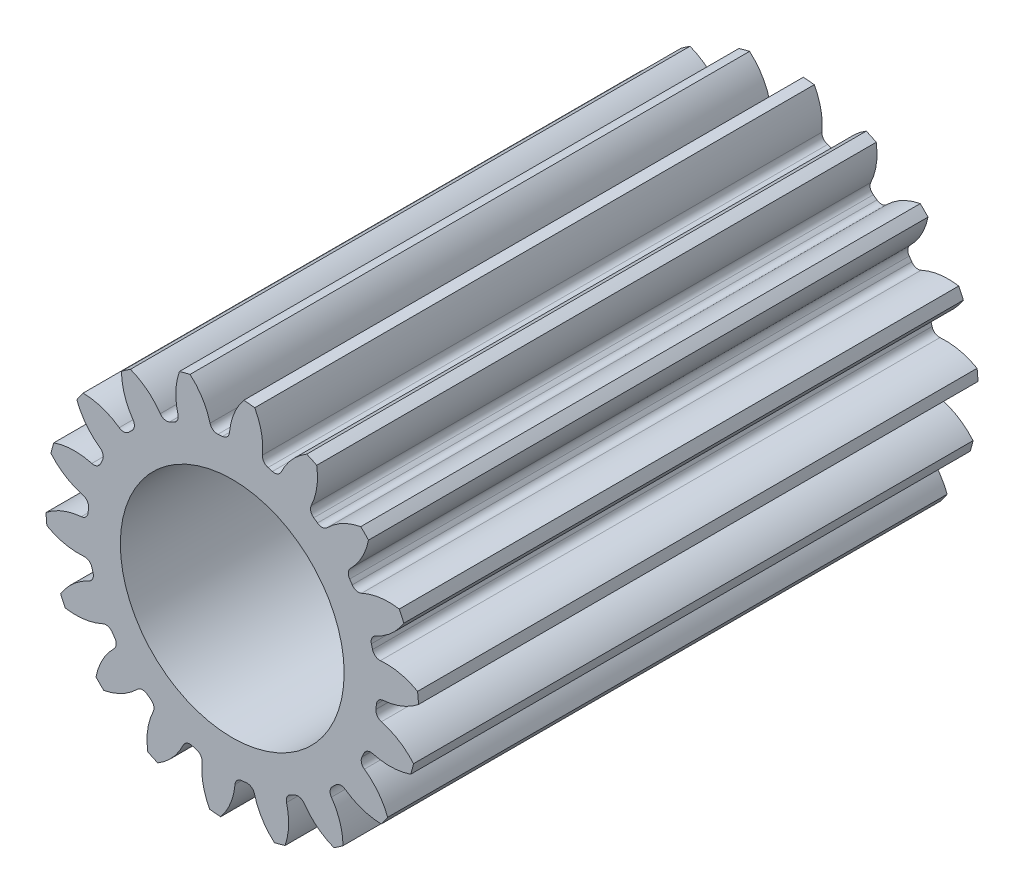
SolidWorks part; units mm, degrees
material "AISI 1045 Steel, cold drawn"
ref_plane "Front" through (0, 0, 0) normal (0, 0, 1) x (1, 0, 0)
ref_plane "Top" through (0, 0, 0) normal (0, 1, 0) x (1, 0, 0)
ref_plane "Right" through (0, 0, 0) normal (1, 0, 0) x (0, 0, -1)
sketch "Sketch3" plane through (0, 0, 0) normal (0, 0, 1) x (1, 0, 0)
  circle A0 centre (0, 0) radius 10
  dimension "od" = 20
extrude "gearBody" add sketch "Sketch3" along normal blind 30
sketch "Sketch2" plane through (0, 0, 0) normal (0, 0, 1) x (1, 0, 0)
  line L0 (0, 0) -> (7.8135, 3.2364) construction
  line L1 (10.2652, -3.2048) -> (0, 0) construction
  line L2 (0, 0) -> (36.3143, 0) construction
  line L3 (9, -0.0203) -> (8.8534, -1.6177) construction
  line L5 (8.9267, -0.819) -> (0, 0) construction
  line L7 (0, 0) -> (8.4572, 0) construction
  arc A0 (8.4555, -0.1697) -> (8.3452, -1.3717) centre (0, 0) ccw construction
  arc A1 (9.9857, 0.5354) -> (9.7215, -2.3435) centre (0, 0) ccw construction
  arc A2 (9, -0.0203) -> (8.8534, -1.6177) centre (0, 0) ccw construction
  arc A3 (7.7047, -0.8296) -> (7.727, -0.5863) centre (0, 0) ccw
  arc A4 (10.2652, -3.2048) -> (7.9976, -1.2579) centre (7.0941, -4.6042) ccw
  arc A5 (10.2652, -3.2048) -> (10.677, 1.2834) centre (0, 0) ccw
  arc A6 (10.677, 1.2834) -> (8.093, -0.2184) centre (7.8135, 3.2364) cw
  arc A7 (7.727, -0.5863) -> (8.093, -0.2184) centre (8.1252, -0.6165) cw
  arc A8 (7.9976, -1.2579) -> (7.7047, -0.8296) centre (8.1017, -0.8723) cw
  point P6 (10.677, 1.2834)
  point P22 (10.2652, -3.2048)
  dimension "baseDia" = 16.9145
  dimension "od" = 20
  dimension "pd" = 18
  dimension "rd" = 15.4984
  dimension "rFillet" = 0.3993
  dimension "pointX" = 10.677
  dimension "pointY" = 1.2834
  dimension "CTT" = 1.5974
  dimension "flankCenterAngle" = 22.5
extrude "toothCut" cut sketch "Sketch2" along normal through all
pattern_circular "CirPattern1" count 18 over 360 about axis through (0, 0, 30) along (0, 0, -1) of "toothCut"
ref_axis "toothSpace" through (0, 0, 0) along (0.9958, -0.0914, 0)
ref_axis "Axis2" through (9.6482, -2.629, 0) along (-0.9648, 0.2629, 0)
sketch "hub1Dia" plane through (0, 0, 0) normal (0, 0, -1) x (-1, 0, 0)
  circle A0 centre (0, 0) radius 0.5
  dimension "hub1Dia" = 1
sketch "hub2Dia" plane through (0, 0, 30) normal (0, 0, 1) x (1, 0, 0)
  circle A0 centre (0, 0) radius 0.5
  dimension "hub2dia" = 1
sketch "boreDia" plane through (0, 0, 0) normal (0, 0, 1) x (1, 0, 0)
  circle A0 centre (0, 0) radius 6
  dimension "boreDia" = 12
extrude "bore" cut sketch "boreDia" against normal mid plane 25400
sketch "kwy1sketch" plane through (0, 0, 0) normal (0, 0, 1) x (1, 0, 0)
  line L0 (-5.2713, 1.1117) -> (0, 0) construction
  line L1 (6.9525, -0.9552) -> (6.7462, -1.9337)
  line L2 (6.7462, -1.9337) -> (5.5231, -1.6758)
  line L3 (6.9525, -0.9552) -> (5.7294, -0.6973)
  line L4 (5.5231, -1.6758) -> (0, 0)
  line L5 (0, 0) -> (5.7294, -0.6973)
  line L6 (0, 0) -> (7.7168, -0.708) construction
  line L7 (6.8493, -1.4445) -> (0, 0) construction
  arc A7 (7.7047, -0.8296) -> (7.727, -0.5863) centre (0, 0) ccw construction
  point P9 (6.8493, -1.4445)
  point P13 (-0.8793, 0.1854)
  dimension "kwy1width" = 1
  dimension "kwy1depth" = 7
  dimension "kwy1angle" = 6.667
  dimension "kwy1Depth2" = 1.25
sketch "kwy2sketch" plane through (0, 0, 0) normal (0, 0, 1) x (1, 0, 0)
  line L0 (7.7168, -0.708) -> (0, 0) construction
  line L1 (0, 0) -> (-3.119, -2.0325) construction
  line L2 (5.5916, 4.2407) -> (6.1376, 3.4029)
  line L3 (6.1376, 3.4029) -> (5.0904, 2.7204)
  line L4 (5.5916, 4.2407) -> (4.5444, 3.5582)
  line L5 (5.0904, 2.7204) -> (0, 0)
  line L6 (0, 0) -> (4.5444, 3.5582)
  arc A2 (7.7047, -0.8296) -> (7.727, -0.5863) centre (0, 0) ccw construction
  point P10 (5.8646, 3.8218)
  dimension "kwy2angle" = 38.333
  dimension "kwy2Width" = 1
  dimension "kwy2depth" = 7
  dimension "kwy2Depth2" = 1.25
sketch "kwy3sketch" plane through (0, 0, 0) normal (0, 0, 1) x (1, 0, 0)
  line L0 (7.7168, -0.708) -> (0, 0) construction
  line L1 (0, 0) -> (-0.5558, -2.6353) construction
  line L2 (0.9552, 6.9525) -> (1.9337, 6.7462)
  line L3 (1.9337, 6.7462) -> (1.6758, 5.5231)
  line L4 (0.9552, 6.9525) -> (0.6973, 5.7294)
  line L5 (1.6758, 5.5231) -> (0, 0)
  line L6 (0.6973, 5.7294) -> (0, 0)
  point P10 (1.4445, 6.8493)
  dimension "kwy3angle" = 83.333
  dimension "kwy3depth" = 7
  dimension "kwy3width" = 1
  dimension "kwy3Depth2" = 1.25
sketch "kwy4sketch" plane through (0, 0, 0) normal (0, 0, 1) x (1, 0, 0)
  line L0 (7.7168, -0.708) -> (0, 0) construction
  line L1 (0, 0) -> (1.1497, -1.7643) construction
  line L2 (-3.4029, 6.1376) -> (-4.2407, 5.5916)
  line L3 (-4.2407, 5.5916) -> (-3.5582, 4.5444)
  line L4 (-3.5582, 4.5444) -> (0, 0)
  line L5 (-2.7204, 5.0904) -> (0, 0)
  line L6 (-3.4029, 6.1376) -> (-2.7204, 5.0904)
  point P15 (-3.8218, 5.8646)
  dimension "kwy4angle" = 128.333
  dimension "kwy4depth" = 7
  dimension "kwy4width" = 1
  dimension "kwy4Depth2" = 1.25
sketch "kwy5sketch" plane through (0, 0, 0) normal (0, 0, 1) x (1, 0, 0)
  line L0 (7.7168, -0.708) -> (0, 0) construction
  line L1 (0, 0) -> (1.7697, -0.3732) construction
  line L2 (-6.7462, 1.9337) -> (-6.9525, 0.9552)
  line L3 (-6.9525, 0.9552) -> (-5.7294, 0.6973)
  line L4 (-6.7462, 1.9337) -> (-5.5231, 1.6758)
  line L5 (-5.7294, 0.6973) -> (0, 0)
  line L6 (-5.5231, 1.6758) -> (0, 0)
  point P10 (-6.8493, 1.4445)
  dimension "kwy5width" = 1
  dimension "kwy5depth" = 7
  dimension "kwy5angle" = 173.333
  dimension "kwy5Depth2" = 1.25
sketch "kwy6sketch" plane through (0, 0, 0) normal (0, 0, 1) x (1, 0, 0)
  line L0 (7.7168, -0.708) -> (0, 0) construction
  line L1 (0, 0) -> (1.514, 0.9867) construction
  line L2 (-6.1376, -3.4029) -> (-5.5916, -4.2407)
  line L3 (-5.5916, -4.2407) -> (-4.5444, -3.5582)
  line L4 (-6.1376, -3.4029) -> (-5.0904, -2.7204)
  line L5 (-4.5444, -3.5582) -> (0, 0)
  line L6 (-5.0904, -2.7204) -> (0, 0)
  point P10 (-5.8646, -3.8218)
  dimension "kwy6angle" = 218.333
  dimension "kwy6width" = 1
  dimension "kwy6depth" = 7
  dimension "kwy6Depth2" = 1.25
sketch "kwy7sketch" plane through (0, 0, 0) normal (0, 0, 1) x (1, 0, 0)
  line L0 (7.7168, -0.708) -> (0, 0) construction
  line L1 (0, 0) -> (0.4178, 1.981) construction
  line L2 (-1.9337, -6.7462) -> (-0.9552, -6.9525)
  line L3 (-1.9337, -6.7462) -> (-1.6758, -5.5231)
  line L4 (-0.9552, -6.9525) -> (-0.6973, -5.7294)
  line L5 (-1.6758, -5.5231) -> (0, 0)
  line L6 (-0.6973, -5.7294) -> (0, 0)
  point P10 (-1.4445, -6.8493)
  dimension "kwy7angle" = 83.333
  dimension "kwy7width" = 1
  dimension "kwy7depth" = 7
  dimension "kwy7angle1" = 263.333
  dimension "kwy7Depth2" = 1.25
sketch "kwy8sketch" plane through (0, 0, 0) normal (0, 0, 1) x (1, 0, 0)
  line L0 (7.7168, -0.708) -> (0, 0) construction
  line L1 (0, 0) -> (-0.9821, 1.507) construction
  line L2 (3.4029, -6.1376) -> (4.2407, -5.5916)
  line L3 (4.2407, -5.5916) -> (3.5582, -4.5444)
  line L4 (3.4029, -6.1376) -> (2.7204, -5.0904)
  line L5 (3.5582, -4.5444) -> (0, 0)
  line L6 (2.7204, -5.0904) -> (0, 0)
  point P10 (3.8218, -5.8646)
  dimension "kwy8angle" = 308.333
  dimension "kwy8width" = 1
  dimension "kwy8depth" = 7
  dimension "kwy8Depth2" = 1.25
sketch "centerLine" plane through (0, 0, 0) normal (0, 1, 0) x (1, 0, 0)
  line L0 (0, 36.4807) -> (0, -59.6309) construction
ref_plane "CB1plane" through (0, 0, 0) normal (0, 0, -1) x (-1, 0, 0)
sketch "CB1diameter" plane through (0, 0, 0) normal (0, 0, -1) x (-1, 0, 0)
  circle A0 centre (0, 0) radius 0.5
  dimension "CB1diameter" = 1
ref_plane "CB2plane" through (0, 0, 30) normal (0, 0, 1) x (1, 0, 0)
sketch "CB2diameter" plane through (0, 0, 30) normal (0, 0, 1) x (1, 0, 0)
  circle A0 centre (0, 0) radius 0.5
  dimension "CB2diameter" = 1
ref_axis "Axis1" through (0, 0, 50) along (0, 0, -1)
sketch3d "3DSketch1" plane through (0, 0, 0) normal (0, 0, 1) x (1, 0, 0)
